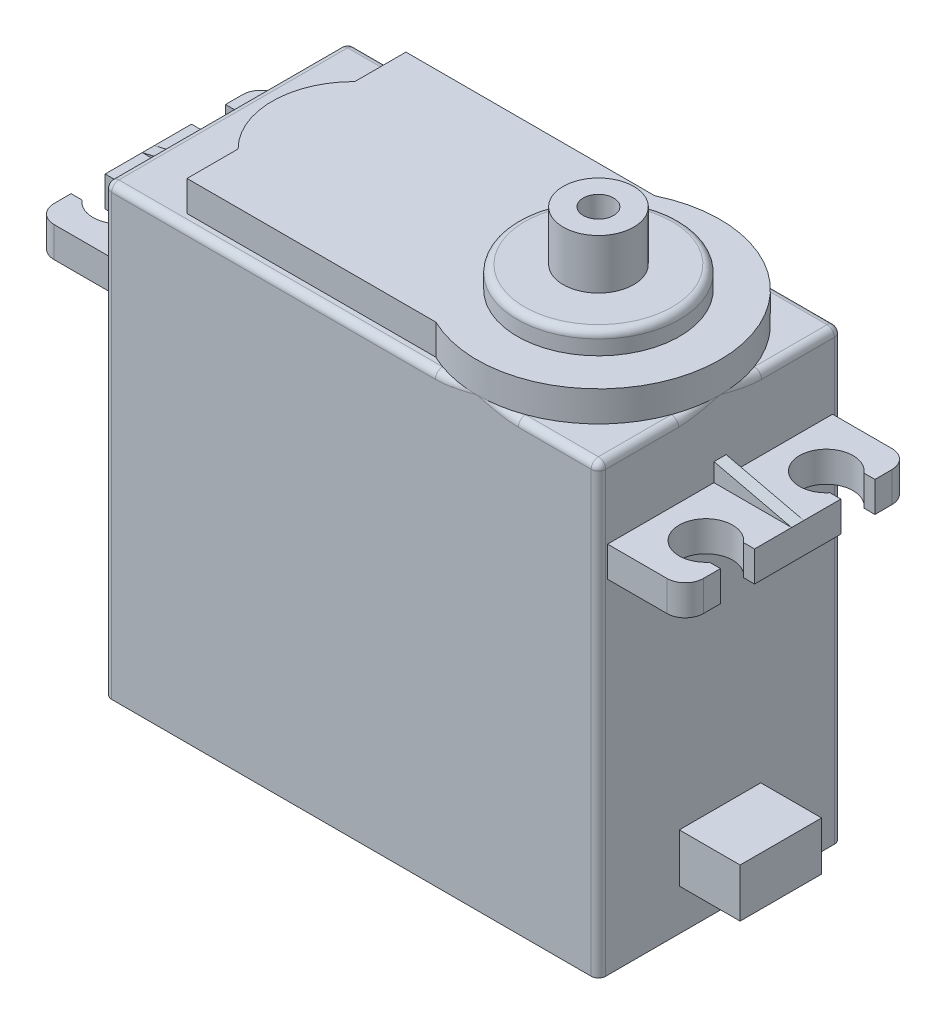
SolidWorks part; units mm, degrees
ref_plane "Front Plane" through (0, 0, 0) normal (0, 0, 1) x (1, 0, 0)
ref_plane "Top Plane" through (0, 0, 0) normal (0, 1, 0) x (1, 0, 0)
ref_plane "Right Plane" through (0, 0, 0) normal (1, 0, 0) x (0, 0, -1)
sketch "Sketch1" plane through (0, 0, 0) normal (0, 1, 0) x (1, 0, 0)
  line L1 (-20.315, -10) -> (20.315, -10)
  line L2 (-20.315, -10) -> (-20.315, 10)
  line L3 (-20.315, 10) -> (20.315, 10)
  line L4 (20.315, -10) -> (20.315, 10)
  line L5 (-20.315, -10) -> (20.315, 10) construction
  line L6 (-20.315, 10) -> (20.315, -10) construction
  point P0 (0, 0)
  dimension "D1" = 20
  dimension "D2" = 40.63
extrude "Boss-Extrude1" add sketch "Sketch1" along normal blind 36.7
sketch "Sketch2" plane through (0, 36.7, 0) normal (0, 1, 0) x (1, 0, 0)
  line L0 (0, 17.0178) -> (0, -19.2095) construction
  line L1 (-20.315, 9.25) -> (-25.2, 9.25)
  line L3 (-25.2, -9.25) -> (-20.315, -9.25)
  line L4 (-20.315, -9.25) -> (-20.315, 9.25)
  line L5 (-24.1, 9.25) -> (-24.1, -9.25) construction
  line L6 (-28.32, 0) -> (-20.315, 0) construction
  line L9 (-25.7971, -3.55) -> (-26.7, -3.55)
  line L10 (-25.7971, -6.35) -> (-26.7, -6.35)
  line L17 (-20.315, 10) -> (-20.315, -10) construction
  line L18 (-26.7, 7.75) -> (-26.7, 6.35)
  line L19 (-25.7971, 6.35) -> (-26.7, 6.35)
  line L20 (-25.7971, 3.55) -> (-26.7, 3.55)
  line L21 (-26.7, 3.55) -> (-26.7, -3.55)
  line L22 (-26.7, -6.35) -> (-26.7, -7.75)
  line L23 (28.32, 0) -> (20.315, 0) construction
  line L24 (24.1, 9.25) -> (24.1, -9.25) construction
  line L25 (26.7, -6.35) -> (26.7, -7.75)
  line L26 (26.7, 3.55) -> (26.7, -3.55)
  line L27 (25.7971, 3.55) -> (26.7, 3.55)
  line L28 (25.7971, 6.35) -> (26.7, 6.35)
  line L29 (26.7, 7.75) -> (26.7, 6.35)
  line L30 (25.7971, -6.35) -> (26.7, -6.35)
  line L31 (25.7971, -3.55) -> (26.7, -3.55)
  line L32 (20.315, -9.25) -> (20.315, 9.25)
  line L33 (25.2, -9.25) -> (20.315, -9.25)
  line L34 (20.315, 9.25) -> (25.2, 9.25)
  arc A0 (-25.7971, 3.55) -> (-25.7971, 6.35) centre (-24.1, 4.95) ccw
  arc A1 (-25.7971, -3.55) -> (-25.7971, -6.35) centre (-24.1, -4.95) cw
  arc A2 (25.7971, -3.55) -> (25.7971, -6.35) centre (24.1, -4.95) ccw
  arc A3 (25.7971, 3.55) -> (25.7971, 6.35) centre (24.1, 4.95) cw
  arc A4 (26.7, -7.75) -> (25.2, -9.25) centre (25.2, -7.75) cw
  arc A5 (26.7, 7.75) -> (25.2, 9.25) centre (25.2, 7.75) ccw
  arc A6 (-26.7, -7.75) -> (-25.2, -9.25) centre (-25.2, -7.75) ccw
  arc A7 (-25.2, 9.25) -> (-26.7, 7.75) centre (-25.2, 7.75) ccw
  point P43 (-26.2485, 3.55)
  point P46 (26.7, -9.25)
  point P49 (26.7, 9.25)
  point P52 (-26.7, -9.25)
  point P55 (-26.7, 9.25)
  dimension "D3" = 2.2
  dimension "D4" = 48.2
  dimension "D8" = 1.5
  dimension "D1" = 18.5
  dimension "D2" = 9.9
  dimension "D5" = 53.4
  dimension "D6" = 2.8
  dimension "D7" = 2.8
extrude "screw_holder" add sketch "Sketch2" along normal blind 2.5 from offset 8.5 offset against normal yes
sketch "Sketch3" plane through (0, 0, 10) normal (0, 0, 1) x (1, 0, 0)
  line L0 (-26.7, 30.7) -> (-20.315, 32.2)
  line L1 (-20.315, 36.7) -> (-20.315, 0) construction
  line L2 (-20.315, 32.2) -> (-20.315, 30.7)
  line L3 (-20.315, 30.7) -> (-26.7, 30.7)
  line L4 (0, 36.7) -> (0, 0) construction
  line L5 (-20.315, 36.7) -> (20.315, 36.7) construction
  line L6 (-20.315, 0) -> (20.315, 0) construction
  line L7 (20.315, 32.2) -> (20.315, 30.7)
  line L8 (20.315, 30.7) -> (26.7, 30.7)
  line L9 (26.7, 30.7) -> (20.315, 32.2)
  dimension "D1" = 1.5
extrude "flaps" add sketch "Sketch3" along normal blind 0.5 and the other way blind 0.5 from surface starting at plane "Front Plane"
sketch "Sketch5" plane through (0, 36.7, 0) normal (0, 1, 0) x (1, 0, 0)
  line L0 (-20.315, 0) -> (20.315, 0) construction
  line L1 (-20.315, 0.5) -> (-20.315, -0.5) construction
  line L2 (20.315, 0.5) -> (20.315, -0.5) construction
  line L3 (20.315, -10) -> (20.315, 10) construction
  line L4 (5.9561, 9) -> (-14.515, 9)
  line L5 (-14.515, 9) -> (-14.515, 4.8)
  line L6 (-14.515, -9) -> (5.9561, -9)
  line L7 (-14.515, -4.8) -> (-14.515, -9)
  line L8 (-20.315, 10) -> (-20.315, -10) construction
  arc A0 (5.9561, 9) -> (5.9561, -9) centre (10.315, 0) cw
  arc A1 (-14.515, -4.8) -> (-14.515, 4.8) centre (-9.755, 0) cw
  point P18 (-16.515, 0)
  dimension "D1" = 10
  dimension "D5" = 3.8
  dimension "D2" = 18
  dimension "D3" = 5.8
  dimension "D4" = 9.6
extrude "Boss-Extrude4" add sketch "Sketch5" along normal blind 2.5
fillet "Fillet1" radius 0.6 11 edges at (-5, 36.7, -10) (20.315, 36.7, -5) (15.315, 36.7, 10) (-20.315, 18.35, -10) (-20.315, 18.35, 10) (20.315, 18.35, 10) (20.315, 18.35, -10) (15.315, 36.7, -10) (20.315, 36.7, 5) (-5, 36.7, 10) (-20.315, 36.7, 0)
sketch "Sketch7" plane through (0, 39.2, 0) normal (0, 1, 0) x (1, 0, 0)
  line L0 (-16.515, 0) -> (20.315, 0) construction
  line L1 (20.315, 0.5) -> (20.315, -0.5) construction
  arc A0 (-14.515, 4.8) -> (-14.515, -4.8) centre (-9.755, 0) ccw construction
  circle A1 centre (10.315, 0) radius 6.675
  dimension "D1" = 13.35
  dimension "D2" = 10
extrude "Boss-Extrude5" add sketch "Sketch7" along normal blind 4.3 from surface starting at face at (-7.3782, 36.7, 0)
fillet "Fillet2" radius 0.6 1 edges at (10.315, 41, -6.675)
sketch "Sketch9" plane through (0, 39.2, 0) normal (0, 1, 0) x (1, 0, 0)
  line L0 (-16.515, 0) -> (20.315, 0) construction
  arc A0 (-14.515, 4.8) -> (-14.515, -4.8) centre (-9.755, 0) ccw construction
  arc A1 (5.9561, -9) -> (5.9561, 9) centre (10.315, 0) ccw construction
  circle A2 centre (10.315, 0) radius 2.9
  circle A3 centre (10.315, 0) radius 1.25
  dimension "D1" = 5.8
  dimension "D3" = 2.5
  dimension "D2" = 10
extrude "pinion" add sketch "Sketch9" along normal blind 4.1 from surface starting at face at (10.315, 41, -6.075)
sketch "Sketch11" plane through (20.315, 0, 0) normal (1, 0, 0) x (0, 0, -1)
  line L0 (0, 28.2) -> (0, 0) construction
  line L1 (9.25, 28.2) -> (-9.25, 28.2) construction
  line L3 (-3.35, 3.4) -> (3.35, 3.4)
  line L4 (-3.35, 3.4) -> (-3.35, 7.4)
  line L5 (-3.35, 7.4) -> (3.35, 7.4)
  line L6 (3.35, 3.4) -> (3.35, 7.4)
  line L7 (-3.35, 3.4) -> (3.35, 7.4) construction
  line L8 (-3.35, 7.4) -> (3.35, 3.4) construction
  point P5 (0, 5.4)
  dimension "D1" = 4
  dimension "D2" = 6.7
  dimension "D3" = 24.8
extrude "wire_base" add sketch "Sketch11" along normal blind 5
